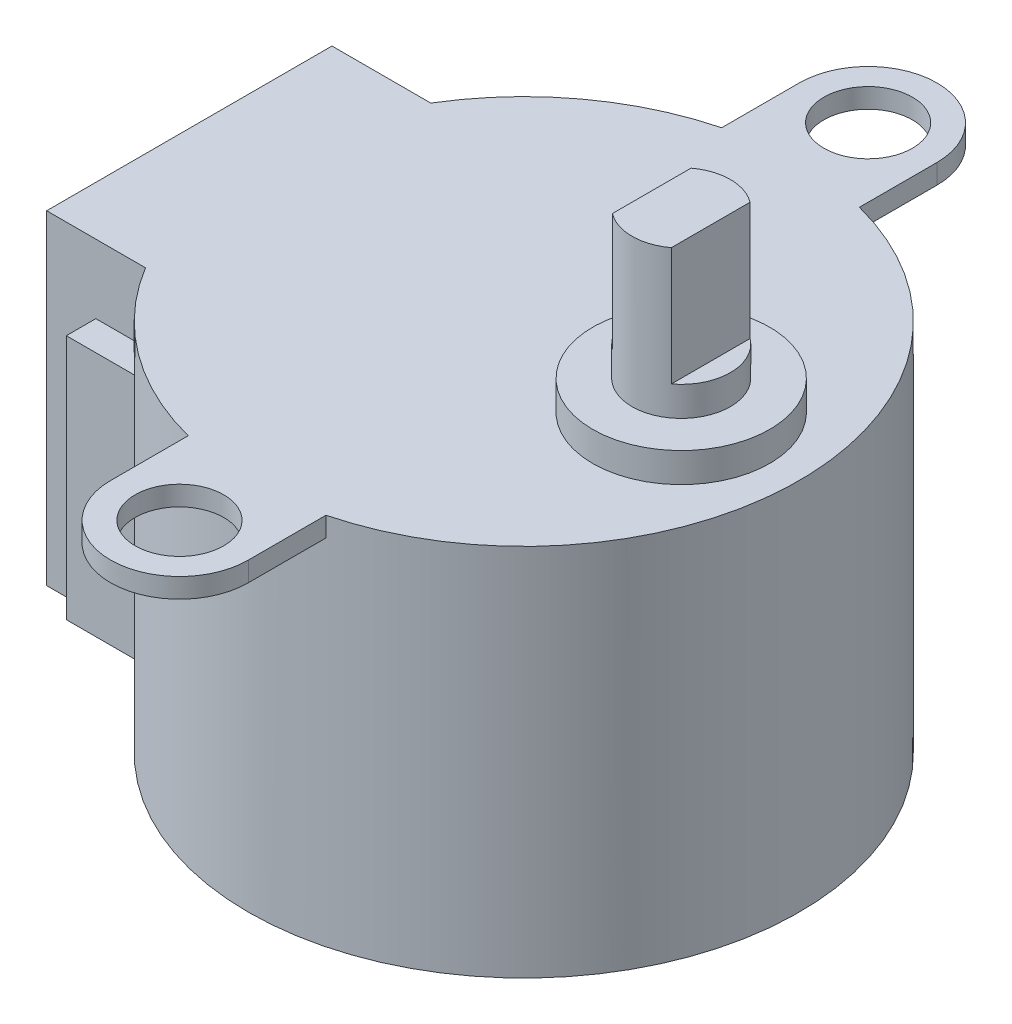
SolidWorks part; units mm, degrees
ref_plane "Front" through (0, 0, 0) normal (0, 0, 1) x (1, 0, 0)
ref_plane "Top" through (0, 0, 0) normal (0, 1, 0) x (1, 0, 0)
ref_plane "Right" through (0, 0, 0) normal (1, 0, 0) x (0, 0, -1)
sketch "Эскиз1" plane through (0, 0, 0) normal (0, 1, 0) x (1, 0, 0)
  line L0 (-14, 0) -> (14, 0) construction
  line L1 (0, 14) -> (0, -14) construction
  line L2 (-3.5, 17.5) -> (-3.5, -17.5)
  line L3 (3.5, 17.5) -> (3.5, -17.5)
  line L4 (6.5, 2) -> (6.5, -2)
  line L5 (9.5, 2) -> (9.5, -2)
  line L7 (-3.5, 7.25) -> (-17, 7.25)
  line L8 (-3.5, 7.25) -> (-3.5, -7.25)
  line L9 (-3.5, -7.25) -> (-17, -7.25)
  line L10 (-17, 7.25) -> (-17, -7.25)
  line L11 (-3.5, 8.75) -> (-14.5, 8.75)
  line L12 (-3.5, 8.75) -> (-3.5, -8.75)
  line L13 (-3.5, -8.75) -> (-14.5, -8.75)
  line L14 (-14.5, 8.75) -> (-14.5, -8.75)
  circle A0 centre (0, 0) radius 14
  circle A1 centre (8, 0) radius 4.5
  circle A2 centre (8, 0) radius 2.5
  circle A3 centre (0, 17.5) radius 2.25
  circle A4 centre (0, 17.5) radius 3.5
  circle A5 centre (0, -17.5) radius 2.25
  circle A6 centre (0, -17.5) radius 3.5
  dimension "D1" = 9
  dimension "D2" = 5
  dimension "D3" = 28
  dimension "D4" = 4.5
  dimension "D5" = 7
  dimension "D6" = 35
  dimension "D7" = 8
  dimension "D8" = 3
  dimension "D9" = 31
  dimension "D10" = 14.5
  dimension "D11" = 17.5
  dimension "D12" = 28.5
extrude "Бобышка-Вытянуть1" add sketch "Эскиз1" along normal blind 9 contours L5 A2 L4 region at (8, 0, 0)
extrude "Бобышка-Вытянуть2" add sketch "Эскиз1<4>" along normal blind 3 contours L4 A2 | L5 A2 region at (6.0922, 0, 0) region at (9.9078, 0, 0)
sketch "Эскиз1<4>" plane through (0, 0, 0) normal (0, 1, 0) x (1, 0, 0) same geometry as "Эскиз1"
extrude "Бобышка-Вытянуть3" add sketch "Эскиз1<5>" along normal blind 1.5 contours A1 A2 region at (8, 0, -4.3727)
sketch "Эскиз1<5>" plane through (0, 0, 0) normal (0, 1, 0) x (1, 0, 0) same geometry as "Эскиз1"
extrude "Бобышка-Вытянуть4" add sketch "Эскиз1<7>" against normal blind 1 separate body contours A4 L2 A0 | A4 A3 | A4 A0 L3 | A6 L3 A0 | A6 A5 | A6 A0 L2 region at (-2.7034, 0, -14.6319) region at (0, 0, -20.901) region at (2.7034, 0, -14.6319) region at (-2.7034, 0, 14.6319) region at (-2.4049, 0, 15.0951) region at (2.7034, 0, 14.6319)
sketch "Эскиз1<7>" plane through (0, 0, 0) normal (0, 1, 0) x (1, 0, 0) same geometry as "Эскиз1"
extrude "Бобышка-Вытянуть5" add sketch "Эскиз1<8>" against normal blind 19 contours L3 A1 A0 | L3 A0 L2 | L2 A0 L11 | L11 A0 L7 L2 | L7 A0 L9 L2 | L9 A0 L13 L2 | L13 A0 L2 | A1 A2 | L5 A2 L4 | L4 A2 | L5 A2 region at (0, 0, 0) region at (-6.2445, 0, -10.5524) region at (-7.4942, 0, -7.9836) region at (-8.4412, 0, 0) region at (-7.4942, 0, 7.9836) region at (-6.2445, 0, 10.5524) region at (8, 0, -4.3727) region at (10.8381, 0, -8.3952) region at (8, 0, 0) region at (6.0922, 0, 0) region at (9.9078, 0, 0)
sketch "Эскиз1<8>" plane through (0, 0, 0) normal (0, 1, 0) x (1, 0, 0) same geometry as "Эскиз1"
extrude "Бобышка-Вытянуть6" add sketch "Эскиз1<9>" against normal blind 16.5 contours L14 L7 L10 L9 | A0 L7 L14 L9 region at (-14.1472, 0, 0) region at (-15.75, 0, 0)
sketch "Эскиз1<9>" plane through (0, 0, 0) normal (0, 1, 0) x (1, 0, 0) same geometry as "Эскиз1"
extrude "Бобышка-Вытянуть7" add sketch "Эскиз1<10>" against normal blind 12.5 from offset 3.5 contours A0 L11 L14 L7 | A0 L9 L14 L13 region at (-12.9734, 0, -8.0433) region at (-12.9734, 0, 8.0433) offset against normal yes
sketch "Эскиз1<10>" plane through (0, 0, 0) normal (0, 1, 0) x (1, 0, 0) same geometry as "Эскиз1"
